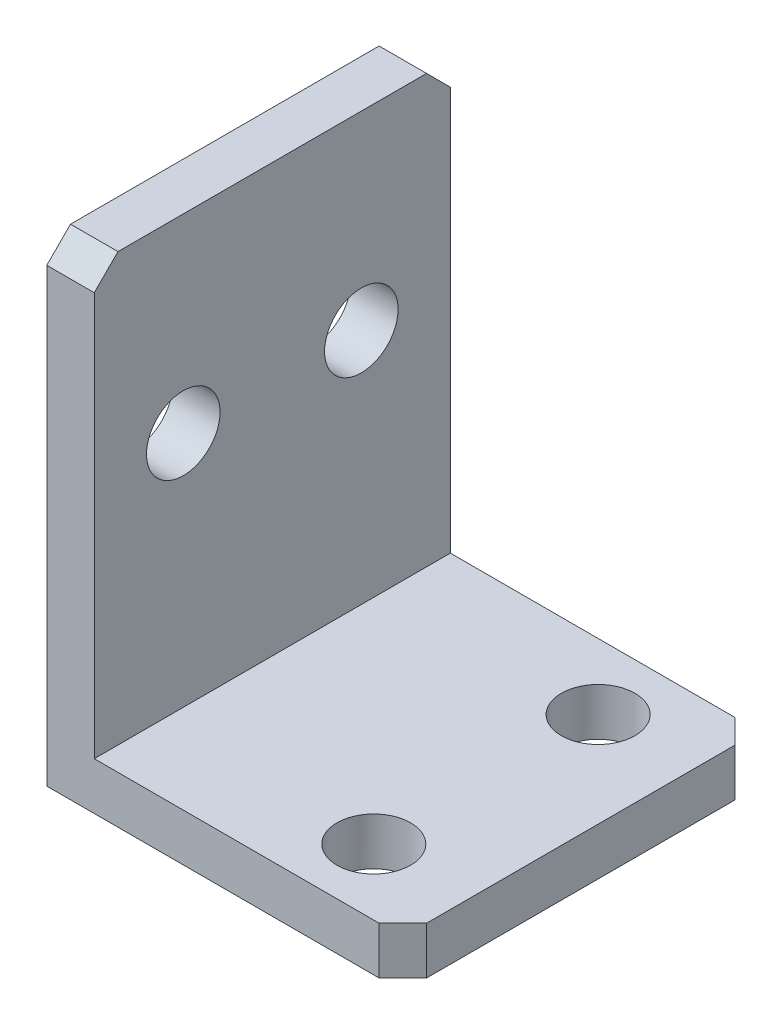
SolidWorks part; units mm, degrees
material "6061 Alloy"
ref_plane "Front Plane" through (0, 0, 0) normal (0, 0, 1) x (1, 0, 0)
ref_plane "Top Plane" through (0, 0, 0) normal (0, 1, 0) x (1, 0, 0)
ref_plane "Right Plane" through (0, 0, 0) normal (1, 0, 0) x (0, 0, -1)
sketch "Sketch1" plane through (0, 0, 0) normal (0, 0, 1) x (1, 0, 0)
  line L0 (0, 0) -> (0, 20)
  line L1 (0, 20) -> (2, 20)
  line L2 (2, 20) -> (2, 2)
  line L3 (2, 2) -> (15, 2)
  line L4 (15, 2) -> (15, 0)
  line L5 (15, 0) -> (0, 0)
  dimension "D1" = 15
  dimension "D2" = 20
  dimension "D3" = 2
extrude "Body" add sketch "Sketch1" along normal blind 15
sketch "Sketch2" plane through (2, 0, 0) normal (1, 0, 0) x (0, 0, -1)
  line L0 (-15, 20) -> (0, 20) construction
  line L1 (-7.5, 20) -> (-7.5, 15.9172) construction
  line L2 (-15, 0) -> (0, 0) construction
  circle A0 centre (-11.25, 12) radius 1.55
  circle A1 centre (-3.75, 12) radius 1.55
  dimension "D3" = 7.5
  dimension "D4" = 12
extrude "ForCarriage" cut sketch "Sketch2" against normal up to surface (2 mm away) up to face at (0, 10, 7.5)
sketch "Sketch3" plane through (0, 2, 0) normal (0, 1, 0) x (1, 0, 0)
  line L0 (15, -7.5) -> (7.2009, -7.5) construction
  line L1 (15, -15) -> (15, 0) construction
  line L2 (0, -15) -> (0, 0) construction
  circle A0 centre (11, -2.775) radius 1.55
  circle A1 centre (11, -12.225) radius 1.55
  dimension "D1" = 3.1
  dimension "D3" = 9.45
  dimension "D4" = 11
extrude "ForSensor" cut sketch "Sketch3" against normal up to surface (2 mm away) up to face at (7.5, 0, 7.5)
chamfer "Chamfer1" distance 1 angle 45 4 edges at (15, 1, 0) (15, 1, 15) (1, 20, 0) (1, 20, 15)
equation "\"D1@Sketch3\"=\"D1@Sketch2\""
